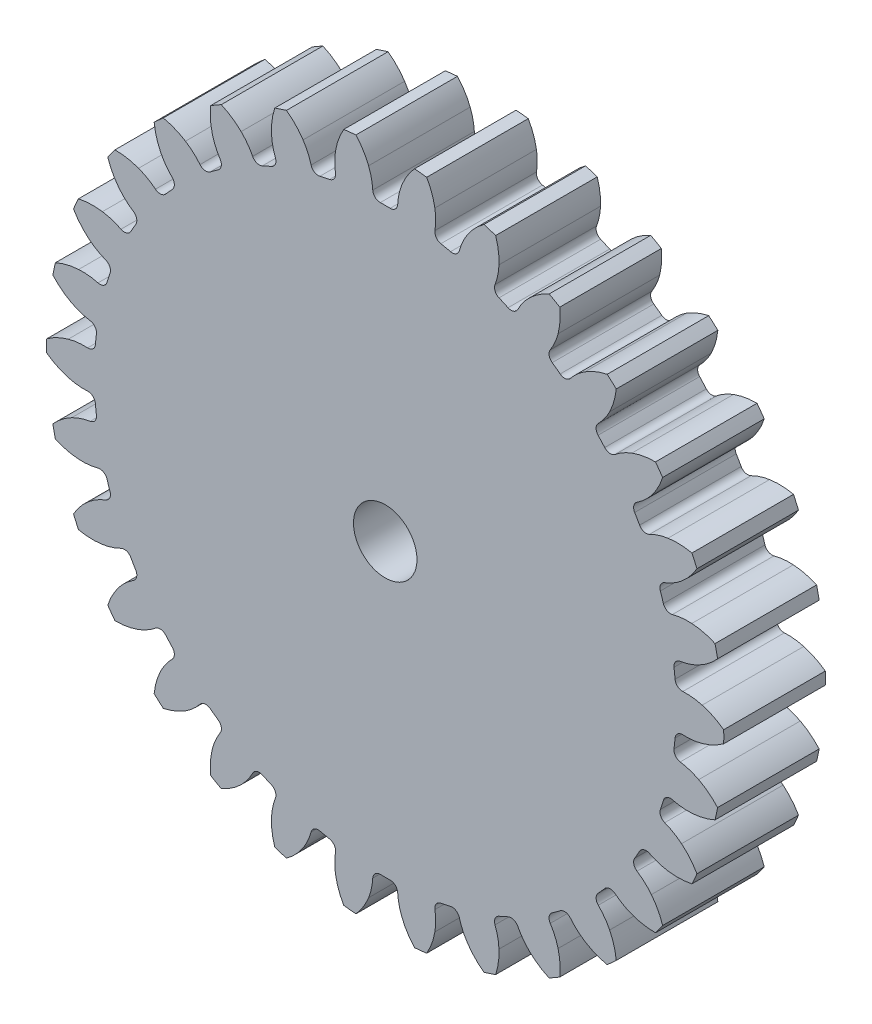
SolidWorks part; units mm, degrees
ref_plane "Front Plane" through (0, 0, 0) normal (0, 0, 1) x (1, 0, 0)
ref_plane "Top Plane" through (0, 0, 0) normal (0, 1, 0) x (1, 0, 0)
ref_plane "Right Plane" through (0, 0, 0) normal (1, 0, 0) x (0, 0, -1)
sketch "Sketch1" plane through (0, 0, 0) normal (0, 0, 1) x (1, 0, 0)
  line L0 (0, 0) -> (47.625, 0) construction
  line L1 (47.625, 0) -> (50.8, 0) construction
  circle A0 centre (0, 0) radius 50.8
  circle A1 centre (0, 0) radius 47.625 construction
  dimension "D2" = 95.25
  dimension "D1" = 3.175
extrude "GEAR_BASE" add sketch "Sketch1" along normal mid plane 15.24
sketch "Sketch2" plane through (0, 0, 7.62) normal (0, 0, 1) x (1, 0, 0)
  line L0 (0, 0) -> (43.6562, 0) construction
  line L1 (43.6562, 0) -> (47.625, 0) construction
  line L2 (0, 0) -> (-50.8, 0) construction
  line L3 (0, 0) -> (-47.5597, -2.494) construction
  line L4 (-47.5597, -2.494) -> (-48.4854, 15.1594) construction
  line L5 (0, 0) -> (-49.6899, -10.5619) construction
  line L6 (-47.5597, -2.494) -> (-43.5589, -2.9143) construction
  line L7 (-47.0389, -7.4487) -> (-43.2129, -6.2057) construction
  line L8 (0, 0) -> (-47.0389, -7.4487) construction
  line L9 (-47.5597, -2.494) -> (-50.7917, -0.9177) construction
  line L10 (-47.0389, -7.4487) -> (-49.8726, -9.6625) construction
  line L11 (-47.0389, -7.4487) -> (-46.5204, -9.8882) construction
  line L12 (-47.0389, -7.4487) -> (-44.274, -24.9088) construction
  line L13 (-47.5597, -2.494) -> (-47.5597, 0) construction
  circle A0 centre (0, 0) radius 47.625 construction
  circle A1 centre (0, 0) radius 43.6562 construction
  circle A2 centre (0, 0) radius 50.8 construction
  arc A3 (-49.8726, -9.6625) -> (-50.7917, -0.9177) centre (0, 0) cw
  arc A4 (-43.4883, -3.8254) -> (-44.6549, -2.8132) centre (-44.5953, -3.9228) ccw
  arc A5 (-44.264, -6.5326) -> (-43.3334, -5.2999) centre (-44.4364, -5.4348) ccw
  arc A6 (-43.3334, -5.2999) -> (-43.4883, -3.8254) centre (0, 0) cw
  arc A7 (-49.8726, -9.6625) -> (-47.0389, -7.4487) centre (-42.4148, -16.2882) cw
  arc A8 (-50.7917, -0.9177) -> (-47.5597, -2.494) centre (-44.8744, 7.1137) ccw
  arc A9 (-47.0389, -7.4487) -> (-44.264, -6.5326) centre (-42.8676, -15.4226) cw
  arc A10 (-47.5597, -2.494) -> (-44.6549, -2.8132) centre (-45.1374, 6.173) ccw
  dimension "D1" = 95.25
  dimension "D11" = 1.1112
  dimension "D12" = 9.9758
  dimension "D2" = 3.9688
  dimension "D3" = 12
  dimension "D5" = 9
  dimension "D7" = 9
  dimension "D8" = 4.9821
  dimension "D9" = 20
  dimension "D10" = 20
  dimension "D6" = 2.494
  dimension "D4" = 2.494
extrude "GEAR_CUT" cut sketch "Sketch2" against normal through all
ref_axis "GEAR_AXIS" through (0, 0, -1.397) along (0, 0, 1)
pattern_circular "GEAR_TEETH" count 30 over 360 about axis through (0, 0, -1.397) along (0, 0, 1) of "GEAR_CUT"
sketch "Sketch3" plane through (0, 0, 7.62) normal (0, 0, 1) x (1, 0, 0)
  circle A0 centre (0, 0) radius 4.7625
  dimension "D1" = 9.525
extrude "BORE" cut sketch "Sketch3" against normal through all
equation "\"N_teeth\"= 30"
equation "\"pitch_diameter\"= \"N_teeth\" / \"Pitch\""
equation "\"Pitch\"= 8"
equation "\"addendum\"=1.000/\"Pitch\""
equation "\"face_width\"=0.23"
equation "\"deddendum\"=1.250/\"Pitch\""
equation "\"tooth_thickness\"=1.571/\"Pitch\""
equation "\"Pressure_Angle\"=20.000000"
equation "\"base_fillet\"=0.35/\"Pitch\""
equation "\"D1@Sketch1\"=\"addendum\""
equation "\"D2@Sketch1\"=\"pitch_diameter\""
equation "\"D1@GEAR_BASE\"=\"GMaterial\""
equation "\"D1@Sketch2\"= \"pitch_diameter\""
equation "\"D2@Sketch2\"=\"deddendum\""
equation "\"D4@Sketch2\"=\"tooth_thickness\"/2"
equation "\"D6@Sketch2\"=\"tooth_thickness\"/2"
equation "\"D9@Sketch2\"=\"Pressure_Angle\""
equation "\"D10@Sketch2\"=\"Pressure_Angle\""
equation "\"D11@Sketch2\"=\"base_fillet\""
equation "\"D12@Sketch2\"=2*\"tooth_thickness\""
equation "\"D3@Sketch2\" = 360 / \"N_teeth\""
equation "\"D1@GEAR_TEETH\" = \"N_teeth\""
equation "\"MDF\"= .6"
equation "\"Foamcore\"= .1"
equation "\"GMaterial\"= \"MDF\""
